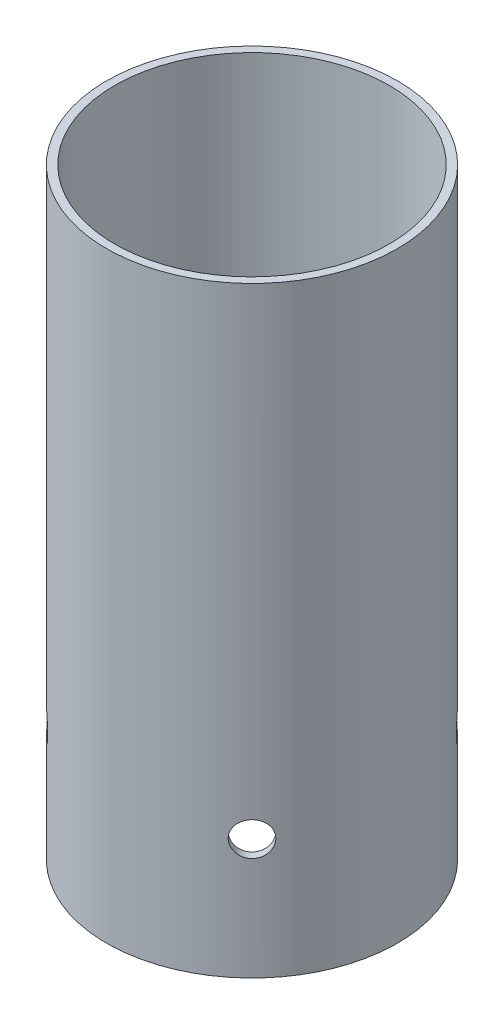
SolidWorks part; units mm, degrees
other "Top Tube"
ref_plane "Front Plane" through (0, 0, 0) normal (0, 0, 1) x (1, 0, 0)
ref_plane "Top Plane" through (0, 0, 0) normal (0, 1, 0) x (1, 0, 0)
ref_plane "Right Plane" through (0, 0, 0) normal (1, 0, 0) x (0, 0, -1)
sketch "Sketch1" plane through (0, 0, 0) normal (0, 0, 1) x (1, 0, 0)
  line L0 (55, 0) -> (-55, 0) construction
  line L1 (-15.35, 254) -> (-14.5, 254)
  line L2 (-15.35, 254) -> (-15.35, 317.5)
  line L3 (-15.35, 317.5) -> (-14.5, 317.5)
  line L4 (-14.5, 254) -> (-14.5, 317.5)
  line L5 (0, -55) -> (0, 55) construction
  line L6 (15.35, 317.5) -> (14.5, 317.5)
  line L7 (15.35, 254) -> (15.35, 317.5)
  line L8 (15.35, 254) -> (14.5, 254)
  line L9 (14.5, 254) -> (14.5, 317.5)
  line L10 (0, 0) -> (0, 330.2)
  dimension "D1" = 63.5
  dimension "9" = 254
  dimension "D2" = 30.7
  dimension "D3" = 29
revolve "Revolve1" add sketch "Sketch1" angle 360 about L10 region at (-14.925, 285.75, 0)
ref_plane "Plane1" through (-10.8541, 0, 10.8541) normal (-0.7071, 0, 0.7071) x (0, -1, 0)
sketch "Sketch2" plane through (-10.8541, 0, 10.8541) normal (-0.7071, 0, 0.7071) x (0, -1, 0)
  line L0 (-254, -15.35) -> (-254, 15.35) construction
  circle A0 centre (-266.7, 0) radius 1.778
  point P4 (0, 0)
  dimension "D1" = 3.556
  dimension "D2" = 12.7
extrude "Cut-Extrude1" cut sketch "Sketch2" against normal blind 2.54
pattern_circular "CirPattern1" count 4 over 360 about axis through (0, 317.5, 0) along (0, -1, 0) of "Cut-Extrude1"
